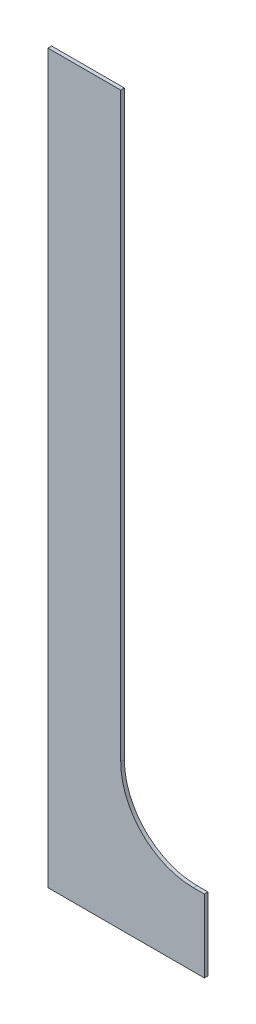
SolidWorks part; units mm, degrees
ref_plane "前视基准面" through (0, 0, 0) normal (0, 0, 1) x (1, 0, 0)
ref_plane "上视基准面" through (0, 0, 0) normal (0, 1, 0) x (1, 0, 0)
ref_plane "右视基准面" through (0, 0, 0) normal (1, 0, 0) x (0, 0, -1)
sketch "草图1" plane through (0, 0, 0) normal (0, 0, 1) x (1, 0, 0)
  line L0 (0, 0) -> (-21.5, 0)
  line L1 (-21.5, 0) -> (-21.5, 100)
  line L2 (-21.5, 100) -> (-11.5, 100)
  line L3 (-11.5, 100) -> (-11.5, 10)
  line L4 (-11.5, 10) -> (0, 10)
  line L5 (0, 10) -> (0, 0)
  dimension "D1" = 100
  dimension "D2" = 21.5
  dimension "D3" = 10
  dimension "D4" = 10
extrude "凸台-拉伸1" add sketch "草图1" along normal blind 0.5
fillet "圆角1" radius 10 1 edges at (-11.5, 10, 0.25)
